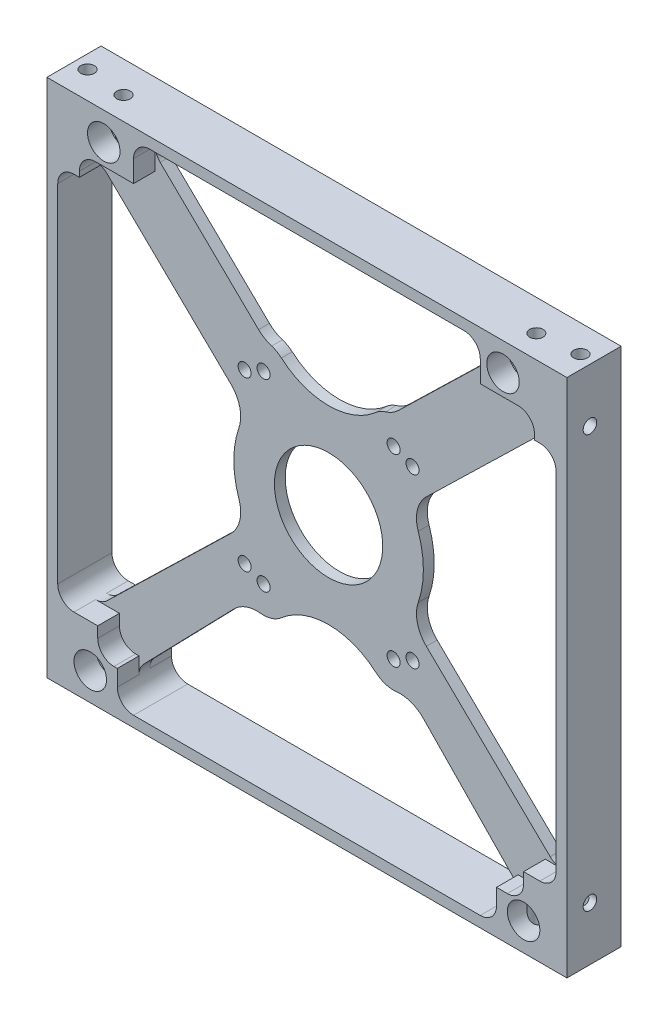
SolidWorks part; units mm, degrees
material "7075-T6 (SN)"
ref_plane "Front Plane" through (0, 0, 0) normal (0, 0, 1) x (1, 0, 0)
ref_plane "Top Plane" through (0, 0, 0) normal (0, 1, 0) x (1, 0, 0)
ref_plane "Right Plane" through (0, 0, 0) normal (1, 0, 0) x (0, 0, -1)
sketch "Sketch1" plane through (0, 0, 0) normal (0, 0, 1) x (1, 0, 0)
  line L0 (-38, 42) -> (-38, 38)
  line L1 (48, -48) -> (-48, -48)
  line L2 (48, -48) -> (48, 48)
  line L3 (48, 48) -> (-48, 48)
  line L4 (-48, -48) -> (-48, 48)
  line L5 (48, -48) -> (-48, 48) construction
  line L6 (48, 48) -> (-48, -48) construction
  line L7 (42, -42) -> (-42, -42)
  line L8 (42, -42) -> (42, 42)
  line L9 (42, 42) -> (-42, 42)
  line L10 (-42, -42) -> (-42, 42)
  line L11 (42, -42) -> (-42, 42) construction
  line L12 (42, 42) -> (-42, -42) construction
  line L13 (-38, 38) -> (-42, 38)
  line L14 (42, 38) -> (38, 38)
  line L15 (38, 38) -> (38, 42)
  line L16 (38, -42) -> (38, -38)
  line L17 (38, -38) -> (42, -38)
  line L18 (-42, -38) -> (-38, -38)
  line L19 (-38, -38) -> (-38, -42)
  point P0 (0, 0)
  point P6 (0, 0)
  point P26 (0, 0)
  dimension "D1" = 96
  dimension "D2" = 96
  dimension "D3" = 6
  dimension "D4" = 84
  dimension "D5" = 10
  dimension "D6" = 4
extrude "Boss-Extrude1" add sketch "Sketch1" along normal blind 10 contours L4 L1 L2 L3 L7 L10 L9 L8 region at (0, -46.6424, 0)
sketch "Sketch4" plane through (0, 0, 10) normal (0, 0, 1) x (1, 0, 0)
  line L0 (36.2, 42.85) -> (-37.5, 42.85) construction
  line L1 (40, -42.85) -> (-40, -42.85) construction
  line L2 (-40, -42.85) -> (-40, 42.85) construction
  line L3 (-40, 42.85) -> (-37.5, 42.85) construction
  line L4 (40, -42.85) -> (40, 42.85) construction
  line L5 (40, 42.85) -> (36.2, 42.85) construction
  line L6 (-40, 42.85) -> (40, -42.85) construction
  point P4 (0, 0)
  dimension "D1" = 73.7
  dimension "D2" = 2.5
  dimension "D3" = 85.7
  dimension "D4" = 3.8
sketch_block_instance "Block1-1"
sketch_block "Block2"
sketch "Sketch5" plane through (0, 0, 10) normal (0, 0, 1) x (1, 0, 0)
  line L0 (40.7, 38.35) -> (42, 38.35)
  line L1 (-42, 47.35) -> (-33, 47.35)
  line L2 (-42, 47.35) -> (-42, 38.35)
  line L3 (-42, 38.35) -> (-33, 38.35)
  line L4 (-33, 47.35) -> (-33, 38.35)
  line L5 (-42, 47.35) -> (-33, 38.35) construction
  line L6 (-42, 38.35) -> (-33, 47.35) construction
  line L7 (-35.5, -47.35) -> (-44.5, -47.35)
  line L8 (-35.5, -47.35) -> (-35.5, -38.35)
  line L9 (-35.5, -38.35) -> (-44.5, -38.35)
  line L10 (-44.5, -47.35) -> (-44.5, -38.35)
  line L11 (-35.5, -47.35) -> (-44.5, -38.35) construction
  line L12 (-35.5, -38.35) -> (-44.5, -47.35) construction
  line L13 (44.5, -47.35) -> (35.5, -47.35)
  line L14 (44.5, -47.35) -> (44.5, -38.35)
  line L15 (44.5, -38.35) -> (35.5, -38.35)
  line L16 (35.5, -47.35) -> (35.5, -38.35)
  line L17 (44.5, -47.35) -> (35.5, -38.35) construction
  line L18 (44.5, -38.35) -> (35.5, -47.35) construction
  line L19 (40.7, 38.35) -> (31.7, 38.35)
  line L20 (40.7, 38.35) -> (40.7, 47.35)
  line L21 (40.7, 47.35) -> (31.7, 47.35)
  line L22 (31.7, 38.35) -> (31.7, 47.35)
  line L23 (40.7, 38.35) -> (31.7, 47.35) construction
  line L24 (40.7, 47.35) -> (31.7, 38.35) construction
  line L25 (42, -42) -> (42, 42) construction
  line L26 (42, 38.35) -> (42, 42)
  line L27 (42, 42) -> (40.7, 42)
  line L28 (42, 42) -> (-42, 42) construction
  point P0 (-37.5, 42.85)
  point P1 (36.2, 42.85)
  point P3 (40, -42.85)
  point P5 (-40, -42.85)
  point P7 (-37.5, 42.85)
  point P13 (-40, -42.85)
  point P18 (40, -42.85)
  point P23 (36.2, 42.85)
  line M13 (42, -42) -> (-42, -42)
  line M14 (-42, -42) -> (-42, 42)
  line M15 (-42, 42) -> (42, 42)
  line M16 (42, 42) -> (42, -42)
  dimension "D1" = 9
  dimension "D2" = 9
  dimension "D3" = 9
  dimension "D4" = 9
  dimension "D5" = 9
  dimension "D6" = 9
  dimension "D7" = 9
  dimension "D8" = 9
extrude "Boss-Extrude2" add sketch "Sketch5" against normal up to surface (10 mm away) contours L22 L19 L20 M15 | L20 L0 M16 M15 | L4 L3 M15 M14 | L8 L9 M14 M13 | L16 L15 M13 M16 region at (41.35, 40.175, 10) region at (36.2, 40.175, 10) region at (38.75, -40.175, 10) region at (-37.5, 40.175, 10) region at (-38.75, -40.175, 10) up to face at (0, 0, 0)
fillet "Fillet1" radius 3 8 edges at (-42, 38.35, 5) (-33, 42, 5) (31.7, 42, 5) (42, 38.35, 5) (35.5, -42, 5) (42, -38.35, 5) (-35.5, -42, 5) (-42, -38.35, 5)
ref_plane "Plane1" through (0, 0, 5) normal (0, 0, -1) x (-1, 0, 0)
sketch "Sketch7" plane through (0, 0, 0) normal (0, 0, -1) x (-1, 0, 0)
  point P0 (-40, -42.85)
  point P2 (40, -42.85)
  point P4 (37.5, 42.85)
  point P6 (-36.2, 42.85)
hole_wizard "M3 Clearance Hole1" positions "3DSketch1" profile "Sketch8" hole size "M3" standard "ISO" end condition through all
sketch3d "3DSketch1"
  point P0 (36.2, 42.85, 0)
  point P3 (-37.5, 42.85, 0)
  point P6 (-40, -42.85, 0)
  point P9 (40, -42.85, 0)
sketch "Sketch8" plane through (36.2, 42.85, 0) normal (1, 0, 0) x (0, 1, 0)
  line L0 (0, 0) -> (0, 10)
  line L1 (0, 10) -> (1.7, 10)
  line L2 (1.7, 10) -> (1.7, 0)
  line L5 (1.7, 0) -> (0, 0)
  line L11 (0, -6.35) -> (0, 107.95) construction
  dimension "Thru Hole Dia." = 3.4
  dimension "Thru Hole Depth" = 10
sketch "Sketch9" plane through (0, 0, 10) normal (0, 0, 1) x (1, 0, 0)
  circle A0 centre (-37.5, 42.85) radius 3
  circle A1 centre (36.2, 42.85) radius 3
  circle A2 centre (-40, -42.85) radius 3
  circle A3 centre (40, -42.85) radius 3
  dimension "D1" = 6
  dimension "D3" = 6
  dimension "D4" = 6
  dimension "D2" = 6
extrude "Cut-Extrude1" cut sketch "Sketch9" against normal blind 4
sketch "Sketch10" plane through (0, -48, 0) normal (0, -1, 0) x (1, 0, 0)
  line L0 (48, 5) -> (32, 5) construction
  line L1 (48, 10) -> (48, 0) construction
  line L2 (-48, 5) -> (-32, 5) construction
  line L3 (-48, 10) -> (-48, 0) construction
  dimension "D1" = 16
  dimension "D2" = 16
ref_plane "Plane2" through (0, 0, 0) normal (0.7071, 0.7071, 0) x (0.7071, -0.7071, 0)
ref_plane "Plane3" through (0, 0, 0) normal (-0.7071, 0.7071, 0) x (0, 0, 1)
ref_axis "Axis1" through (0, 0, -0.5) along (0, 0, 1)
sketch "Sketch14" plane through (0, -48, 0) normal (0, -1, 0) x (1, 0, 0)
  line L0 (-48, 5) -> (-45.5, 5) construction
  line L1 (-48, 10) -> (-48, 0) construction
  line L2 (48, 5) -> (45.5, 5) construction
  line L3 (48, 10) -> (48, 0) construction
  dimension "D1" = 2.5
  dimension "D2" = 2.5
hole_wizard "M3 Tapped Hole2" positions "3DSketch3" profile "Sketch15" tap size "M3" standard "ISO"
sketch3d "3DSketch3"
  point P0 (45.5, -48, 5)
  point P3 (-45.5, -48, 5)
sketch "Sketch15" plane through (45.5, -48, 5) normal (1, 0, 0) x (0, 0, -1)
  line L0 (0, 0) -> (0, 10.2511)
  line L1 (0, 10.2511) -> (1.25, 9.5)
  line L2 (1.25, 9.5) -> (1.25, 0)
  line L5 (1.25, 0) -> (0, 0)
  line L10 (0, 10.2511) -> (-1.25, 9.5) construction
  line L11 (0, -6.35) -> (0, 107.95) construction
  dimension "Tap Drill Dia." = 2.5
  dimension "Tap Drill Depth" = 9.5
  dimension "Drill Angle" = 118
cosmetic thread "Hole Thread3" parameters "D1"=8, "D2"=3
cosmetic thread "Hole Thread4" parameters "D1"=8, "D2"=3
mirror "Mirror2" about plane through (0, 0, 0) normal (0, 1, 0) of "M3 Tapped Hole2"
sketch "Sketch19" plane through (0, 0, 0) normal (0, 0, -1) x (-1, 0, 0)
  line L12 (-32.5, -42) -> (32.5, -42)
  line L13 (-35.5, -38.35) -> (-35.5, -39)
  line L14 (-39, -38.35) -> (-35.5, -38.35)
  line L15 (-42, 35.35) -> (-42, -35.35)
  line L16 (-31.7, 38.35) -> (-39, 38.35)
  line L17 (-31.7, 39) -> (-31.7, 38.35)
  line L18 (30, 42) -> (-28.7, 42)
  line L19 (33, 38.35) -> (33, 39)
  line L20 (39, 38.35) -> (33, 38.35)
  line L21 (42, -35.35) -> (42, 35.35)
  line L22 (35.5, -38.35) -> (39, -38.35)
  line L23 (35.5, -39) -> (35.5, -38.35)
  line L24 (-32.5, -42) -> (32.5, -42)
  line L25 (-35.5, -38.35) -> (-35.5, -39)
  line L26 (-39, -38.35) -> (-35.5, -38.35)
  line L27 (-42, 35.35) -> (-42, -35.35)
  line L28 (-31.7, 38.35) -> (-39, 38.35)
  line L29 (-31.7, 39) -> (-31.7, 38.35)
  line L30 (30, 42) -> (-28.7, 42)
  line L31 (33, 38.35) -> (33, 39)
  line L32 (39, 38.35) -> (33, 38.35)
  line L33 (42, -35.35) -> (42, 35.35)
  line L34 (35.5, -38.35) -> (39, -38.35)
  line L35 (35.5, -39) -> (35.5, -38.35)
  arc A8 (-35.5, -39) -> (-32.5, -42) centre (-32.5, -39) ccw
  arc A9 (-42, -35.35) -> (-39, -38.35) centre (-39, -35.35) ccw
  arc A10 (-39, 38.35) -> (-42, 35.35) centre (-39, 35.35) ccw
  arc A11 (-28.7, 42) -> (-31.7, 39) centre (-28.7, 39) ccw
  arc A12 (33, 39) -> (30, 42) centre (30, 39) ccw
  arc A13 (42, 35.35) -> (39, 38.35) centre (39, 35.35) ccw
  arc A14 (39, -38.35) -> (42, -35.35) centre (39, -35.35) ccw
  arc A15 (32.5, -42) -> (35.5, -39) centre (32.5, -39) ccw
  arc A16 (-35.5, -39) -> (-32.5, -42) centre (-32.5, -39) ccw
  arc A17 (-42, -35.35) -> (-39, -38.35) centre (-39, -35.35) ccw
  arc A18 (-39, 38.35) -> (-42, 35.35) centre (-39, 35.35) ccw
  arc A19 (-28.7, 42) -> (-31.7, 39) centre (-28.7, 39) ccw
  arc A20 (33, 39) -> (30, 42) centre (30, 39) ccw
  arc A21 (42, 35.35) -> (39, 38.35) centre (39, 35.35) ccw
  arc A22 (39, -38.35) -> (42, -35.35) centre (39, -35.35) ccw
  arc A23 (32.5, -42) -> (35.5, -39) centre (32.5, -39) ccw
  dimension "D1" = 0
extrude "Boss-Extrude3" add sketch "Sketch19" against normal up to surface (10 mm away) up to face at (39.2, 42.85, 10)
sketch "Sketch17" plane through (-48, 0, 0) normal (-1, 0, 0) x (0, 0, 1)
  point P0 (5.752, -38.1)
  point P1 (5.752, 38.1)
sketch "Sketch18" plane through (0, 0, 0) normal (0, 0, -1) x (-1, 0, 0)
  line L0 (-48, -48) -> (-48, 48) construction
  line L1 (48, -48) -> (35, -48)
  line L2 (48, -48) -> (48, -35)
  line L3 (48, -35) -> (35, -35)
  line L4 (35, -48) -> (35, -35)
  line L6 (-35, -46) -> (-35, -48)
  line L7 (-35, -48) -> (35, -48)
  line L8 (35, -46) -> (35, -48)
  line L9 (-35, -48) -> (-48, -48)
  line L10 (-35, -48) -> (-35, -35)
  line L11 (-35, -35) -> (-48, -35)
  line L12 (-48, -48) -> (-48, -35)
  line L13 (-48, 48) -> (48, 48) construction
  line L14 (35, -46) -> (-35, -46)
  line L16 (29, 46) -> (-33.0121, 46)
  line L17 (-35, -46) -> (-35, 46)
  line L18 (48, -48) -> (48, 48) construction
  line L19 (-35, 35) -> (-32, 35)
  line L20 (-35, 35) -> (-35, 46)
  line L21 (-35, 46) -> (-32, 46)
  line L22 (-32, 35) -> (-32, 46)
  line L23 (-43, -35) -> (-35, -35)
  line L24 (-46, -32) -> (-46, 32)
  line L25 (-43, 35) -> (-35, 35)
  line L26 (-35, -35) -> (-35, 35)
  line L29 (35, 35) -> (32, 35)
  line L30 (32, 43) -> (32, 35)
  line L31 (35, 35) -> (43, 35)
  line L32 (35, 35) -> (35, -35)
  line L33 (35, -35) -> (43, -35)
  line L34 (46, 32) -> (46, -32)
  line L36 (-35, -35) -> (-40, -35)
  line L37 (-35, -35) -> (-35, -40)
  line L38 (-35, -40) -> (-37, -40)
  line L39 (-40, -35) -> (-40, -37)
  line L40 (35, -35) -> (38.6149, -35)
  line L41 (35, -35) -> (35, -40)
  line L42 (35, -40) -> (35.6149, -40)
  line L43 (38.6149, -35) -> (38.6149, -37)
  line L48 (-21.1373, 35) -> (-32, 35)
  line L49 (-21.1373, 35) -> (-21.1373, 46)
  line L50 (-21.1373, 46) -> (-29, 46)
  line L51 (-32, 35) -> (-32, 43)
  line L52 (32, 35) -> (42, 35)
  line L53 (32, 35) -> (32, 39)
  line L54 (32, 39) -> (39, 39)
  line L55 (42, 35) -> (42, 36)
  line L56 (-32, 35) -> (-42, 35)
  line L57 (-32, 35) -> (-32, 39)
  line L58 (-32, 39) -> (-39, 39)
  line L59 (-42, 35) -> (-42, 36)
  arc A0 (35.6149, -40) -> (38.6149, -37) centre (35.6149, -37) ccw
  arc A1 (-37, -40) -> (-40, -37) centre (-37, -37) cw
  arc A2 (-43, -35) -> (-46, -32) centre (-43, -32) cw
  arc A3 (-46, 32) -> (-43, 35) centre (-43, 32) cw
  arc A6 (43, 35) -> (46, 32) centre (43, 32) cw
  arc A7 (43, -35) -> (46, -32) centre (43, -32) ccw
  arc A8 (-29, 46) -> (-32, 43) centre (-29, 43) ccw
  arc A9 (29, 46) -> (32, 43) centre (29, 43) cw
  arc A10 (39, 39) -> (42, 36) centre (39, 36) cw
  arc A11 (-39, 39) -> (-42, 36) centre (-39, 36) ccw
  point P39 (38.6149, -40)
  point P44 (-46, -35)
  point P57 (46, -35)
  dimension "D15" = 3
  dimension "D16" = 3
  dimension "D17" = 3
  dimension "D22" = 3
  dimension "D1" = 13
  dimension "D2" = 13
  dimension "D4" = 13
  dimension "D5" = 13
  dimension "D3" = 2
  dimension "D6" = 2
  dimension "D7" = 3
  dimension "D8" = 13
  dimension "D9" = 2
  dimension "D11" = 2
  dimension "D12" = 8
  dimension "D13" = 8
  dimension "D14" = 3.6149
  dimension "D10" = 3
  dimension "D18" = 6
  dimension "D19" = 9
  dimension "D20" = 9
  dimension "D21" = 6
extrude "Cut-Extrude2" cut sketch "Sketch18" against normal blind 10 contours A9 L16 L49 L48 L19 L17 L10 L14 L4 L32 L29 L30 | L16 A8 L22 L48 L49 | L3 A7 L34 A6 L31 L32 L33 | A3 L24 A2 L23 L11 L17 L25 | L42 A0 L43 L33 L4 | A1 L38 L17 L11 L39 | L53 L52 L55 A10 L54 | L57 L56 L59 A11 L58 region at (-0.4981, -1.2155, 0) region at (-40.4756, 0, 0) region at (-36.6714, -37.2811, 0) region at (37.3468, -37.3468, 0) region at (40.4756, 0, 0) region at (26.4904, 40.4206, 0)
fillet "Fillet2" radius 3 2 edges at (35, -46, 5) (-35, -46, 5)
hole_wizard "M3 Tapped Hole3" positions "3DSketch4" profile "Sketch20" tap size "M3" standard "ISO"
sketch3d "3DSketch4"
  point P0 (-48, -38.1, 5.752)
  point P3 (-48, 38.1, 5.752)
sketch "Sketch20" plane through (-48, -38.1, 5.752) normal (0, 1, 0) x (0, 0, 1)
  line L0 (0, 0) -> (0, 8.2511)
  line L1 (0, 8.2511) -> (1.25, 7.5)
  line L2 (1.25, 7.5) -> (1.25, 0)
  line L5 (1.25, 0) -> (0, 0)
  line L10 (0, 8.2511) -> (-1.25, 7.5) construction
  line L11 (0, -6.35) -> (0, 107.95) construction
  dimension "Tap Drill Dia." = 2.5
  dimension "Tap Drill Depth" = 7.5
  dimension "Drill Angle" = 118
cosmetic thread "Hole Thread9" parameters "D1"=3.0702, "D2"=3
cosmetic thread "Hole Thread10" parameters "D1"=3.0702, "D2"=3
pattern_circular "CirPattern1" count 4 every 90 about axis through (0, 0, -0.5) along (0, 0, 1) of "M3 Tapped Hole3"
sketch "Sketch21" plane through (0, 0, 5) normal (0, 0, -1) x (-1, 0, 0)
  line L20 (46, -32) -> (46, 32)
  line L21 (38.6149, -35) -> (43, -35)
  line L22 (38.6149, -37) -> (38.6149, -35)
  line L23 (35, -40) -> (35.6149, -40)
  line L24 (35, -43) -> (35, -40)
  line L25 (-32, -46) -> (32, -46)
  line L26 (-35, -40) -> (-35, -43)
  line L27 (-37, -40) -> (-35, -40)
  line L28 (-40, -35) -> (-40, -37)
  line L29 (-43, -35) -> (-40, -35)
  line L30 (-46, 32) -> (-46, -32)
  line L31 (-42, 35) -> (-43, 35)
  line L32 (-42, 36) -> (-42, 35)
  line L33 (-32, 39) -> (-39, 39)
  line L34 (-32, 43) -> (-32, 39)
  line L35 (29, 46) -> (-29, 46)
  line L36 (32, 39) -> (32, 43)
  line L37 (39, 39) -> (32, 39)
  line L38 (42, 35) -> (42, 36)
  line L39 (43, 35) -> (42, 35)
  line L40 (46, -32) -> (46, 32)
  line L41 (38.6149, -35) -> (43, -35)
  line L42 (38.6149, -37) -> (38.6149, -35)
  line L43 (35, -40) -> (35.6149, -40)
  line L44 (35, -43) -> (35, -40)
  line L45 (-32, -46) -> (32, -46)
  line L46 (-35, -40) -> (-35, -43)
  line L47 (-37, -40) -> (-35, -40)
  line L48 (-40, -35) -> (-40, -37)
  line L49 (-43, -35) -> (-40, -35)
  line L50 (-46, 32) -> (-46, -32)
  line L51 (-42, 35) -> (-43, 35)
  line L52 (-42, 36) -> (-42, 35)
  line L53 (-32, 39) -> (-39, 39)
  line L54 (-32, 43) -> (-32, 39)
  line L55 (29, 46) -> (-29, 46)
  line L56 (32, 39) -> (32, 43)
  line L57 (39, 39) -> (32, 39)
  line L58 (42, 35) -> (42, 36)
  line L59 (43, 35) -> (42, 35)
  arc A12 (46, 32) -> (43, 35) centre (43, 32) ccw
  arc A13 (43, -35) -> (46, -32) centre (43, -32) ccw
  arc A14 (35.6149, -40) -> (38.6149, -37) centre (35.6149, -37) ccw
  arc A15 (32, -46) -> (35, -43) centre (32, -43) ccw
  arc A16 (-35, -43) -> (-32, -46) centre (-32, -43) ccw
  arc A17 (-40, -37) -> (-37, -40) centre (-37, -37) ccw
  arc A18 (-46, -32) -> (-43, -35) centre (-43, -32) ccw
  arc A19 (-43, 35) -> (-46, 32) centre (-43, 32) ccw
  arc A20 (-39, 39) -> (-42, 36) centre (-39, 36) ccw
  arc A21 (-29, 46) -> (-32, 43) centre (-29, 43) ccw
  arc A22 (32, 43) -> (29, 46) centre (29, 43) ccw
  arc A23 (42, 36) -> (39, 39) centre (39, 36) ccw
  arc A24 (46, 32) -> (43, 35) centre (43, 32) ccw
  arc A25 (43, -35) -> (46, -32) centre (43, -32) ccw
  arc A26 (35.6149, -40) -> (38.6149, -37) centre (35.6149, -37) ccw
  arc A27 (32, -46) -> (35, -43) centre (32, -43) ccw
  arc A28 (-35, -43) -> (-32, -46) centre (-32, -43) ccw
  arc A29 (-40, -37) -> (-37, -40) centre (-37, -37) ccw
  arc A30 (-46, -32) -> (-43, -35) centre (-43, -32) ccw
  arc A31 (-43, 35) -> (-46, 32) centre (-43, 32) ccw
  arc A32 (-39, 39) -> (-42, 36) centre (-39, 36) ccw
  arc A33 (-29, 46) -> (-32, 43) centre (-29, 43) ccw
  arc A34 (32, 43) -> (29, 46) centre (29, 43) ccw
  arc A35 (42, 36) -> (39, 39) centre (39, 36) ccw
  dimension "D1" = 0
extrude "Boss-Extrude4" add sketch "Sketch21" along normal blind 1 and the other way blind 1
sketch "Sketch22" plane through (0, 0, 4) normal (0, 0, -1) x (-1, 0, 0)
  line L0 (-8.9993, -15.0087) -> (-34.1522, -40.91)
  line L1 (-32, -46) -> (32, -46)
  line L2 (34.1522, -40.91) -> (8.9993, -15.0087)
  line L3 (0, 0) -> (-29.2584, -30.1289) construction
  line L4 (0, -46) -> (0, 0) construction
  line L5 (-8.9993, -15.0087) -> (8.9993, -15.0087) construction
  line L6 (-48, -48) -> (48, -48) construction
  circle A0 centre (0, 0) radius 10
  circle A1 centre (0, 0) radius 17.5
  arc A2 (-34.1522, -40.91) -> (-32, -46) centre (-32, -43) ccw
  arc A3 (32, -46) -> (34.1522, -40.91) centre (32, -43) ccw
  arc A9 (-35, -43) -> (-32, -46) centre (-32, -43) ccw construction
  dimension "D1" = 20
  dimension "D2" = 35
  dimension "D5" = 3
  dimension "D3" = 4
  dimension "D4" = 2
extrude "Cut-Extrude3" cut sketch "Sketch22" against normal blind 11 and the other way blind 1 contours L1 A3 L2 A1 L0 A2 | A0 region at (0, -33.9469, 4) region at (0, 0, 4)
fillet "Fillet3" radius 6 2 edges at (-8.9993, -15.0087, 5) (8.9993, -15.0087, 5)
pattern_circular "CirPattern2" count 2 every 90 about axis through (0, 0, -0.5) along (0, 0, 1) of "Cut-Extrude3", "Fillet3" other way count 2
sketch "Sketch23" plane through (0, 0, 4) normal (0, 0, -1) x (-1, 0, 0)
  line L0 (29, 46) -> (-29, 46)
  line L1 (31.09, 40.8478) -> (7.6401, 18.0755)
  line L2 (18.0429, 11.9458) -> (40.91, 34.1522) construction
  line L3 (-7.6401, 18.0755) -> (-31.09, 40.8478)
  line L4 (-40.91, 34.1522) -> (-18.0429, 11.9458) construction
  circle A0 centre (-29, 43) radius 3
  circle A1 centre (29, 43) radius 3
  arc A7 (32, 43) -> (29, 46) centre (29, 43) ccw construction
  arc A8 (-29, 46) -> (-32, 43) centre (-29, 43) ccw construction
  arc A9 (3.9504, 17.0483) -> (-3.9504, 17.0483) centre (0, 0) ccw
  arc A10 (7.6401, 18.0755) -> (3.9504, 17.0483) centre (4.8534, 20.945) cw
  arc A11 (-3.9504, 17.0483) -> (-7.6401, 18.0755) centre (-4.8534, 20.945) cw
  arc M40 (32, 43) -> (29, 46) centre (29, 43) ccw
  line M41 (29, 46) -> (-29, 46)
  arc M42 (-29, 46) -> (-32, 43) centre (-29, 43) ccw
  dimension "D1" = 6
  dimension "D2" = 6
  dimension "D3" = 17.5
  dimension "D4" = 4
extrude "Cut-Extrude4" cut sketch "Sketch23" against normal blind 10 contours A11 A9 A10 L1 A1 A0 L3 M41 | A1 M40 | A0 M42 region at (0, 34.3208, 4) region at (-29, 43, 4) region at (29, 43, 4)
sketch "Sketch24" plane through (0, 0, 4) normal (0, 0, -1) x (-1, 0, 0)
  line L0 (11.9458, -18.0429) -> (34.1522, -40.91) construction
  line L1 (-15.5, 15.5) -> (15.5, 15.5) construction
  line L2 (-15.5, 15.5) -> (-15.5, -15.5) construction
  line L3 (-15.5, -15.5) -> (15.5, -15.5) construction
  line L4 (15.5, 15.5) -> (15.5, -15.5) construction
  line L5 (-15.5, 15.5) -> (15.5, -15.5) construction
  line L6 (-15.5, -15.5) -> (15.5, 15.5) construction
  line L7 (-12, 17) -> (12, 17) construction
  line L8 (-12, 17) -> (-12, -17) construction
  line L9 (-12, -17) -> (12, -17) construction
  line L10 (12, 17) -> (12, -17) construction
  line L11 (-12, 17) -> (12, -17) construction
  line L12 (-12, -17) -> (12, 17) construction
  line L13 (-34.1522, -40.91) -> (-11.9458, -18.0429) construction
  line L37 (-32, 43) -> (-32, 39)
  line L38 (-32, 39) -> (-39, 39)
  line L39 (-42, 36) -> (-42, 35)
  line L40 (-42, 35) -> (-43, 35)
  line L41 (-40.91, 34.1522) -> (-18.0429, 11.9458)
  line L42 (-18.0429, -11.9458) -> (-40.91, -34.1522)
  line L43 (-43, -35) -> (-40, -35)
  line L44 (-40, -35) -> (-40, -37)
  line L45 (-37, -40) -> (-35, -40)
  line L46 (-35, -40) -> (-35, -43)
  line L47 (-34.1522, -40.91) -> (-11.9458, -18.0429)
  line L48 (11.9458, -18.0429) -> (34.1522, -40.91)
  line L49 (35, -43) -> (35, -40)
  line L50 (35, -40) -> (35.6149, -40)
  line L51 (38.6149, -37) -> (38.6149, -35)
  line L52 (38.6149, -35) -> (43, -35)
  line L53 (40.91, -34.1522) -> (18.0429, -11.9458)
  line L54 (18.0429, 11.9458) -> (40.91, 34.1522)
  line L55 (43, 35) -> (42, 35)
  line L56 (42, 35) -> (42, 36)
  line L57 (39, 39) -> (32, 39)
  line L58 (32, 39) -> (32, 43)
  line L59 (31.09, 40.8478) -> (7.6401, 18.0755)
  line L60 (-7.6401, 18.0755) -> (-31.09, 40.8478)
  line L61 (-32, 43) -> (-32, 39)
  line L62 (-32, 39) -> (-39, 39)
  line L63 (-42, 36) -> (-42, 35)
  line L64 (-42, 35) -> (-43, 35)
  line L65 (-40.91, 34.1522) -> (-18.0429, 11.9458)
  line L66 (-18.0429, -11.9458) -> (-40.91, -34.1522)
  line L67 (-43, -35) -> (-40, -35)
  line L68 (-40, -35) -> (-40, -37)
  line L69 (-37, -40) -> (-35, -40)
  line L70 (-35, -40) -> (-35, -43)
  line L73 (35, -43) -> (35, -40)
  line L74 (35, -40) -> (35.6149, -40)
  line L75 (38.6149, -37) -> (38.6149, -35)
  line L76 (38.6149, -35) -> (43, -35)
  line L77 (40.91, -34.1522) -> (18.0429, -11.9458)
  line L78 (18.0429, 11.9458) -> (40.91, 34.1522)
  line L79 (43, 35) -> (42, 35)
  line L80 (42, 35) -> (42, 36)
  line L81 (39, 39) -> (32, 39)
  line L82 (32, 39) -> (32, 43)
  line L83 (31.09, 40.8478) -> (7.6401, 18.0755)
  line L84 (-7.6401, 18.0755) -> (-31.09, 40.8478)
  arc A5 (14.8932, -21.0779) -> (7.0563, -16.2515) centre (12, -17) cw
  arc A6 (11.9458, -18.0429) -> (5.6905, -16.549) centre (7.6415, -22.2229) ccw construction
  arc A7 (-7.1022, -15.994) -> (-14.8932, -21.0779) centre (-12, -17) cw
  arc A8 (-5.6905, -16.549) -> (5.6905, -16.549) centre (0, 0) ccw construction
  arc A9 (-8.7123, -20.7671) -> (8.7123, -20.7671) centre (0, -30.75) cw
  arc A10 (-5.6905, -16.549) -> (5.6905, -16.549) centre (0, 0) ccw
  arc A29 (-32, 43) -> (-31.09, 40.8478) centre (-29, 43) ccw
  arc A30 (-39, 39) -> (-42, 36) centre (-39, 36) ccw
  arc A31 (-40.91, 34.1522) -> (-43, 35) centre (-43, 32) ccw
  arc A32 (-16.549, 5.6905) -> (-18.0429, 11.9458) centre (-22.2229, 7.6415) ccw
  arc A33 (-16.549, 5.6905) -> (-16.549, -5.6905) centre (0, 0) ccw
  arc A34 (-18.0429, -11.9458) -> (-16.549, -5.6905) centre (-22.2229, -7.6415) ccw
  arc A35 (-43, -35) -> (-40.91, -34.1522) centre (-43, -32) ccw
  arc A36 (-40, -37) -> (-37, -40) centre (-37, -37) ccw
  arc A37 (-34.1522, -40.91) -> (-35, -43) centre (-32, -43) ccw
  arc A38 (-5.6905, -16.549) -> (-11.9458, -18.0429) centre (-7.6415, -22.2229) ccw
  arc A39 (-5.6905, -16.549) -> (5.6905, -16.549) centre (0, 0) ccw
  arc A40 (11.9458, -18.0429) -> (5.6905, -16.549) centre (7.6415, -22.2229) ccw
  arc A41 (35, -43) -> (34.1522, -40.91) centre (32, -43) ccw
  arc A42 (35.6149, -40) -> (38.6149, -37) centre (35.6149, -37) ccw
  arc A43 (40.91, -34.1522) -> (43, -35) centre (43, -32) ccw
  arc A44 (16.549, -5.6905) -> (18.0429, -11.9458) centre (22.2229, -7.6415) ccw
  arc A45 (16.549, -5.6905) -> (16.549, 5.6905) centre (0, 0) ccw
  arc A46 (18.0429, 11.9458) -> (16.549, 5.6905) centre (22.2229, 7.6415) ccw
  arc A47 (43, 35) -> (40.91, 34.1522) centre (43, 32) ccw
  arc A48 (42, 36) -> (39, 39) centre (39, 36) ccw
  arc A49 (31.09, 40.8478) -> (32, 43) centre (29, 43) ccw
  arc A50 (3.9504, 17.0483) -> (7.6401, 18.0755) centre (4.8534, 20.945) ccw
  arc A51 (3.9504, 17.0483) -> (-3.9504, 17.0483) centre (0, 0) ccw
  arc A52 (-7.6401, 18.0755) -> (-3.9504, 17.0483) centre (-4.8534, 20.945) ccw
  arc A53 (-32, 43) -> (-31.09, 40.8478) centre (-29, 43) ccw
  arc A54 (-39, 39) -> (-42, 36) centre (-39, 36) ccw
  arc A55 (-40.91, 34.1522) -> (-43, 35) centre (-43, 32) ccw
  arc A56 (-16.549, 5.6905) -> (-18.0429, 11.9458) centre (-22.2229, 7.6415) ccw
  arc A57 (-16.549, 5.6905) -> (-16.549, -5.6905) centre (0, 0) ccw
  arc A58 (-18.0429, -11.9458) -> (-16.549, -5.6905) centre (-22.2229, -7.6415) ccw
  arc A59 (-43, -35) -> (-40.91, -34.1522) centre (-43, -32) ccw
  arc A60 (-40, -37) -> (-37, -40) centre (-37, -37) ccw
  arc A61 (-34.1522, -40.91) -> (-35, -43) centre (-32, -43) ccw
  arc A65 (35, -43) -> (34.1522, -40.91) centre (32, -43) ccw
  arc A66 (35.6149, -40) -> (38.6149, -37) centre (35.6149, -37) ccw
  arc A67 (40.91, -34.1522) -> (43, -35) centre (43, -32) ccw
  arc A68 (16.549, -5.6905) -> (18.0429, -11.9458) centre (22.2229, -7.6415) ccw
  arc A69 (16.549, -5.6905) -> (16.549, 5.6905) centre (0, 0) ccw
  arc A70 (18.0429, 11.9458) -> (16.549, 5.6905) centre (22.2229, 7.6415) ccw
  arc A71 (43, 35) -> (40.91, 34.1522) centre (43, 32) ccw
  arc A72 (42, 36) -> (39, 39) centre (39, 36) ccw
  arc A73 (31.09, 40.8478) -> (32, 43) centre (29, 43) ccw
  arc A74 (3.9504, 17.0483) -> (7.6401, 18.0755) centre (4.8534, 20.945) ccw
  arc A75 (3.9504, 17.0483) -> (-3.9504, 17.0483) centre (0, 0) ccw
  arc A76 (-7.6401, 18.0755) -> (-3.9504, 17.0483) centre (-4.8534, 20.945) ccw
  point P0 (0, 0)
  point P6 (0, 0)
  line M24 (-34.1522, -40.91) -> (-11.9458, -18.0429)
  arc M25 (-11.9458, -18.0429) -> (-5.6905, -16.549) centre (-7.6415, -22.2229) cw
  arc M26 (-5.6905, -16.549) -> (5.6905, -16.549) centre (0, 0) ccw
  arc M27 (5.6905, -16.549) -> (11.9458, -18.0429) centre (7.6415, -22.2229) cw
  line M28 (11.9458, -18.0429) -> (34.1522, -40.91)
  dimension "D5" = 5
  dimension "D6" = 5
  dimension "D1" = 31
  dimension "D2" = 31
  dimension "D3" = 24
  dimension "D4" = 34
hole_wizard "M2 Clearance Hole1" positions "3DSketch5" profile "Sketch25" hole size "M2" standard "ISO"
sketch3d "3DSketch5"
  point P0 (-15.5, -15.5, 4)
  point P3 (15.5, -15.5, 4)
  point P6 (15.5, 15.5, 4)
  point P9 (-15.5, 15.5, 4)
sketch "Sketch25" plane through (-15.5, -15.5, 4) normal (1, 0, 0) x (0, 1, 0)
  line L0 (0, 0) -> (0, 8.221)
  line L1 (0, 8.221) -> (1.2, 7.5)
  line L2 (1.2, 7.5) -> (1.2, 0)
  line L5 (1.2, 0) -> (0, 0)
  line L10 (0, 8.221) -> (-1.2, 7.5) construction
  line L11 (0, -6.35) -> (0, 107.95) construction
  dimension "Hole Dia." = 2.4
  dimension "Hole Depth" = 7.5
  dimension "Drill Angle" = 118
extrude "Boss-Extrude6" add sketch "Sketch24" against normal up to surface (2 mm away) contours A5 M28 M27 | A7 M25 M24 | A7 A9 M26 M25 | A9 A5 M26 M27 region at (10.4328, -19.2931, 4) region at (5.4616, -17.8182, 4) region at (-5.4616, -17.8182, 4) region at (-10.4328, -19.2931, 4) up to face at (-16.7, -15.5, 6)
fillet "Fillet5" radius 6 2 edges at (-14.8932, -21.0779, 5) (14.8932, -21.0779, 5)
pattern_circular "CirPattern8" count 2 every 180 about axis through (0, 0, -0.5) along (0, 0, 1) of "Boss-Extrude6"
fillet "Fillet6" radius 6 2 edges at (-11.6702, 21.9891, 5) (11.6702, 21.9891, 5)
hole_wizard "M2 Clearance Hole2" positions "3DSketch6" profile "Sketch27" hole size "M2" standard "ISO"
sketch3d "3DSketch6"
  point P0 (-12, -17, 4)
  point P3 (12, -17, 4)
  point P6 (12, 17, 4)
  point P9 (-12, 17, 4)
sketch "Sketch27" plane through (-12, -17, 4) normal (1, 0, 0) x (0, 1, 0)
  line L0 (0, 0) -> (0, 8.221)
  line L1 (0, 8.221) -> (1.2, 7.5)
  line L2 (1.2, 7.5) -> (1.2, 0)
  line L5 (1.2, 0) -> (0, 0)
  line L10 (0, 8.221) -> (-1.2, 7.5) construction
  line L11 (0, -6.35) -> (0, 107.95) construction
  dimension "Hole Dia." = 2.4
  dimension "Hole Depth" = 7.5
  dimension "Drill Angle" = 118
equation "\"D2@Sketch5\"=\"D1@Sketch5\""
equation "\"D4@Sketch5\"=\"D3@Sketch5\""
equation "\"D5@Sketch5\"=\"D3@Sketch5\""
equation "\"D6@Sketch5\"=\"D3@Sketch5\""
equation "\"D8@Sketch5\"=\"D7@Sketch5\""
equation "\"D3@Sketch9\"=\"D1@Sketch9\""
equation "\"D4@Sketch9\"=\"D1@Sketch9\""
equation "\"D2@Sketch9\"=\"D3@Sketch9\""
equation "\"D2@Sketch10\"=\"D1@Sketch10\""
equation "\"D2@Sketch14\"=\"D1@Sketch14\""
equation "\"D4@Sketch18\"=\"D1@Sketch18\""
equation "\"D2@Sketch18\"=\"D1@Sketch18\""
equation "\"D5@Sketch18\"=\"D1@Sketch18\""
equation "\"D6@Sketch18\"=\"D3@Sketch18\""
equation "\"D9@Sketch18\"=\"D3@Sketch18\""
equation "\"D13@Sketch18\"=\"D12@Sketch18\""
equation "\"D21@Sketch18\"=\"D18@Sketch18\""
equation "\"D20@Sketch18\"=\"D19@Sketch18\""
equation "\"D2@Sketch23\"=\"D1@Sketch23\""
equation "\"D2@Sketch24\"=\"D1@Sketch24\""
